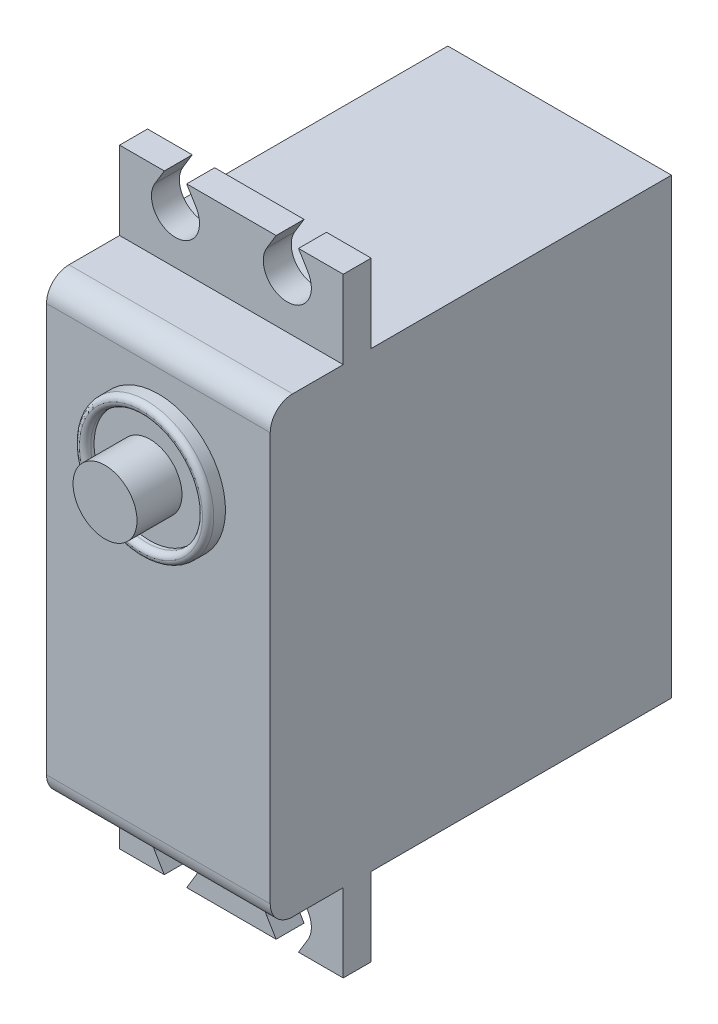
SolidWorks part; units mm, degrees
ref_plane "Front Plane" through (0, 0, 0) normal (0, 0, 1) x (1, 0, 0)
ref_plane "Top Plane" through (0, 0, 0) normal (0, 1, 0) x (1, 0, 0)
ref_plane "Right Plane" through (0, 0, 0) normal (1, 0, 0) x (0, 0, -1)
sketch "Sketch1" plane through (0, 0, 0) normal (1, 0, 0) x (0, 0, -1)
  line L0 (35.88, -20.25) -> (35.88, 20.25)
  line L1 (35.88, 20.25) -> (9.03, 20.25)
  line L2 (9.03, 20.25) -> (9.03, 27.25)
  line L3 (9.03, 27.25) -> (6.53, 27.25)
  line L4 (6.53, 27.25) -> (6.53, 20.25)
  line L5 (0, 18.25) -> (0, -18.25)
  line L6 (35.88, 0) -> (0, 0) construction
  line L7 (6.53, -27.25) -> (6.53, -20.25)
  line L8 (9.03, -27.25) -> (6.53, -27.25)
  line L9 (9.03, -20.25) -> (9.03, -27.25)
  line L10 (35.88, -20.25) -> (9.03, -20.25)
  line L11 (6.53, 20.25) -> (2, 20.25)
  line L12 (6.53, -20.25) -> (2, -20.25)
  arc A2 (2, 20.25) -> (0, 18.25) centre (2, 18.25) ccw
  arc A3 (2, -20.25) -> (0, -18.25) centre (2, -18.25) cw
  dimension "D6" = 2
  dimension "D1" = 7
  dimension "D2" = 2.5
  dimension "D3" = 26.85
  dimension "D4" = 35.88
  dimension "D5" = 40.5
extrude "Boss-Extrude1" add sketch "Sketch1" along normal mid plane 20
sketch "Sketch2" plane through (0, 0, 0) normal (0, 0, 1) x (1, 0, 0)
  line L0 (-10, 10.25) -> (10, 10.25) construction
  line L1 (-10, 18.25) -> (-10, -18.25) construction
  line L2 (10, 18.25) -> (10, -18.25) construction
  line L4 (10, 20.25) -> (-10, 20.25) construction
  circle A0 centre (0, 10.25) radius 6
  circle A1 centre (0, 10.25) radius 5
  circle A2 centre (0, 10.25) radius 2.86
  dimension "D2" = 12
  dimension "D3" = 1
  dimension "D4" = 5.72
  dimension "D1" = 10
extrude "Boss-Extrude2" add sketch "Sketch2" along normal blind 1.55 contours A0
extrude "Cut-Extrude1" cut sketch "Sketch2<3>" against normal blind 0.8 from surface contours L0 A1 A2 | L0 A2 | A2 L0 | A1 L0 A2 | A1 region at (0, 13.2218, 0) region at (0, 9.0362, 0) region at (0, 11.4638, 0) region at (3.93, 10.1382, 0) starting at face at (6, 10.25, 1.55)
sketch "Sketch2<3>" plane through (0, 0, 0) normal (0, 0, 1) x (1, 0, 0) same geometry as "Sketch2"
extrude "Boss-Extrude3" add sketch "Sketch2<4>" along normal blind 4.77 contours A2
sketch "Sketch2<4>" plane through (0, 0, 0) normal (0, 0, 1) x (1, 0, 0) same geometry as "Sketch2"
sketch "Sketch3" plane through (0, 0, -6.53) normal (0, 0, 1) x (1, 0, 0)
  line L0 (0, 27.25) -> (0, 20.25) construction
  line L1 (10, 27.25) -> (-10, 27.25) construction
  line L2 (10, 20.25) -> (-10, 20.25) construction
  line L3 (-5, 24.75) -> (-5, 27.25) construction
  line L4 (-6.8393, 25.8633) -> (-6, 27.25)
  line L5 (-3.1607, 25.8633) -> (-4, 27.25)
  line L6 (3.1607, 25.8633) -> (4, 27.25)
  line L7 (6.8393, 25.8633) -> (6, 27.25)
  line L8 (5, 24.75) -> (-5, 24.75) construction
  circle A0 centre (-5, 24.75) radius 2.15
  circle A1 centre (5, 24.75) radius 2.15
  line M11 (10, 27.25) -> (-10, 27.25)
  dimension "D2" = 4.3
  dimension "D1" = 2
  dimension "D3" = 10
  dimension "D4" = 24.75
extrude "Cut-Extrude2" cut sketch "Sketch3" against normal up to surface (2.5 mm away) contours A0 | A0 L5 L4 M11 | A1 | L6 A1 L7 M11 region at (5, 26.9242, -6.53) region at (-5, 26.9242, -6.53) region at (-5, 24.75, -6.53) region at (5, 24.75, -6.53) up to face at (0, 23.75, -9.03)
mirror "Mirror1" about plane through (0, 0, 0) normal (0, 1, 0) of "Cut-Extrude2"
fillet "Fillet1" radius 0.5 2 edges at (5, 10.25, 1.55) (6, 10.25, 1.55)
